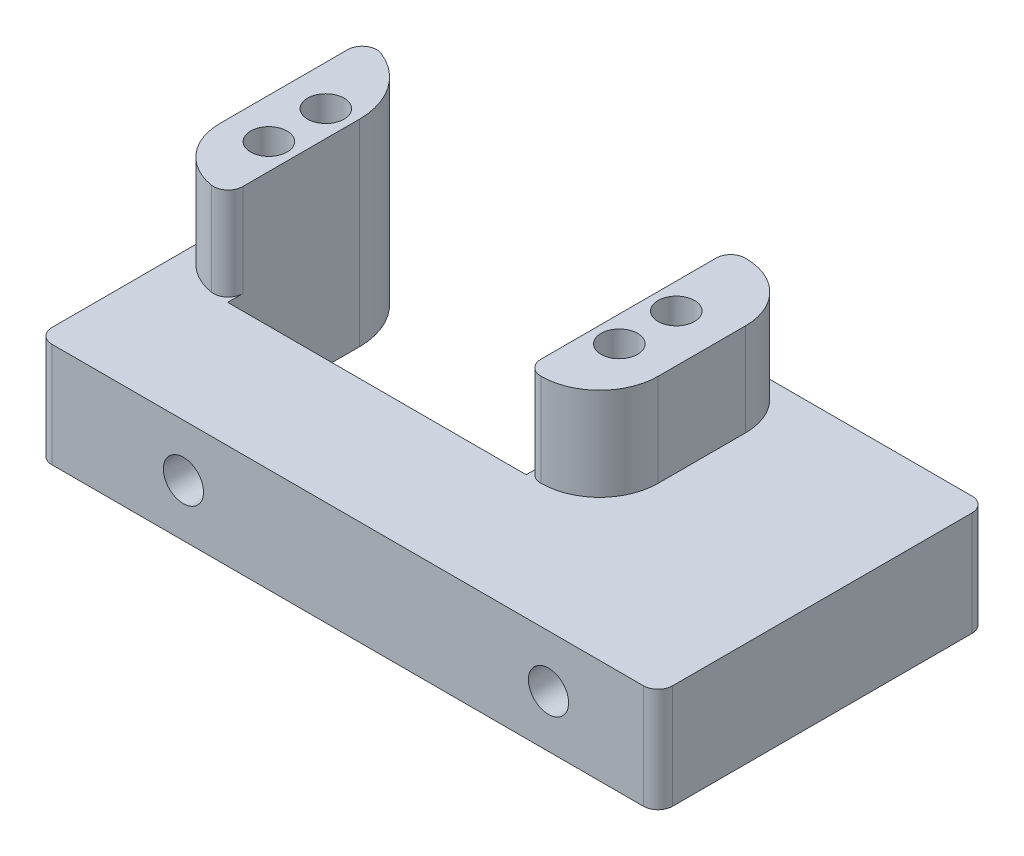
SolidWorks part; units mm, degrees
ref_plane "Front" through (0, 0, 0) normal (0, 0, 1) x (1, 0, 0)
ref_plane "Top" through (0, 0, 0) normal (0, 1, 0) x (1, 0, 0)
ref_plane "Right" through (0, 0, 0) normal (1, 0, 0) x (0, 0, -1)
sketch "Sketch1" plane through (0, 0, 0) normal (0, 1, 0) x (1, 0, 0)
  line L1 (0, 0) -> (85, 0)
  line L2 (0, 0) -> (0, 45)
  line L3 (0, 45) -> (85, 45)
  line L4 (85, 0) -> (85, 45)
  dimension "D1" = 85
  dimension "D2" = 45
extrude "Boss-Extrude1" add sketch "Sketch1" along normal blind 27
sketch "Sketch2" plane through (0, 27, 0) normal (0, 1, 0) x (1, 0, 0)
  line L0 (0, 45) -> (0, 0) construction
  line L1 (85, 45) -> (0, 45) construction
  circle A0 centre (5.5, 34) radius 2.5
  circle A1 centre (53.5, 34) radius 2.5
  circle A2 centre (53.5, 26.2) radius 2.5
  circle A3 centre (5.5, 26.2) radius 2.5
  dimension "D3" = 5
  dimension "D6" = 48
  dimension "D1" = 5.5
  dimension "D2" = 11
  dimension "D7" = 7.8
  dimension "D4" = 2
  dimension "D5" = 2
extrude "Cut-Extrude1" cut sketch "Sketch2" against normal through all
sketch "Sketch4" plane through (0, 0, 0) normal (-1, 0, 0) x (0, 0, 1)
  line L0 (-45, 27) -> (0, 27) construction
  line L1 (0, 27) -> (-17, 27)
  line L2 (0, 27) -> (0, 14.3)
  line L3 (0, 14.3) -> (-17, 14.3)
  line L4 (-17, 27) -> (-17, 14.3)
  line L5 (0, 27) -> (0, 0) construction
  dimension "D1" = 12.7
  dimension "D2" = 17
extrude "Cut-Extrude2" cut sketch "Sketch4" against normal through all
sketch "Sketch5" plane through (0, 0, -17) normal (0, 0, 1) x (1, 0, 0)
  line L0 (85, 14.3) -> (0, 14.3) construction
  line L1 (85, 27) -> (60, 27)
  line L2 (85, 27) -> (85, 14.3)
  line L3 (85, 14.3) -> (60, 14.3)
  line L4 (60, 27) -> (60, 14.3)
  dimension "D1" = 25
extrude "Cut-Extrude3" cut sketch "Sketch5" against normal through all
sketch "Sketch6" plane through (0, 27, 0) normal (0, 1, 0) x (1, 0, 0)
  line L0 (60, 17) -> (0, 17) construction
  line L1 (9.05, 17) -> (49.95, 17)
  line L2 (9.05, 17) -> (9.05, 45)
  line L3 (9.05, 45) -> (49.95, 45)
  line L4 (49.95, 17) -> (49.95, 45)
  line L5 (60, 45) -> (0, 45) construction
  line L6 (29.5, 34) -> (29.5, 45) construction
  line L7 (5.5, 34) -> (53.5, 34) construction
  circle A0 centre (5.5, 34) radius 2.5 construction
  dimension "D1" = 3.55
extrude "Cut-Extrude4" cut sketch "Sketch6" against normal through all
fillet "Fillet1" radius 10 1 edges at (9.05, 13.5, -45)
fillet "Fillet2" radius 8 3 edges at (60, 20.65, -45) (0, 20.65, -17) (60, 20.65, -17)
fillet "Fillet4" radius 2 7 edges at (9.05, 20.65, -17) (49.95, 20.65, -17) (49.95, 13.5, -45) (85, 7.15, -45) (85, 7.15, 0) (0, 7.15, 0) (0, 13.5, -45)
sketch "Sketch7" plane through (0, 0, 0) normal (0, 0, 1) x (1, 0, 0)
  line L0 (20, 0) -> (20, 14.3) construction
  line L1 (2, 0) -> (83, 0) construction
  line L2 (83, 14.3) -> (2, 14.3) construction
  line L3 (85, 14.3) -> (85, 0) construction
  circle A0 centre (70, 7.15) radius 2.75
  circle A1 centre (20, 7.15) radius 2.75
  point P4 (15.8808, 4.8102)
  point P11 (22.1942, 0)
  dimension "D3" = 5.5
  dimension "D1" = 50
  dimension "D2" = 15
extrude "Cut-Extrude5" cut sketch "Sketch7" against normal through all
